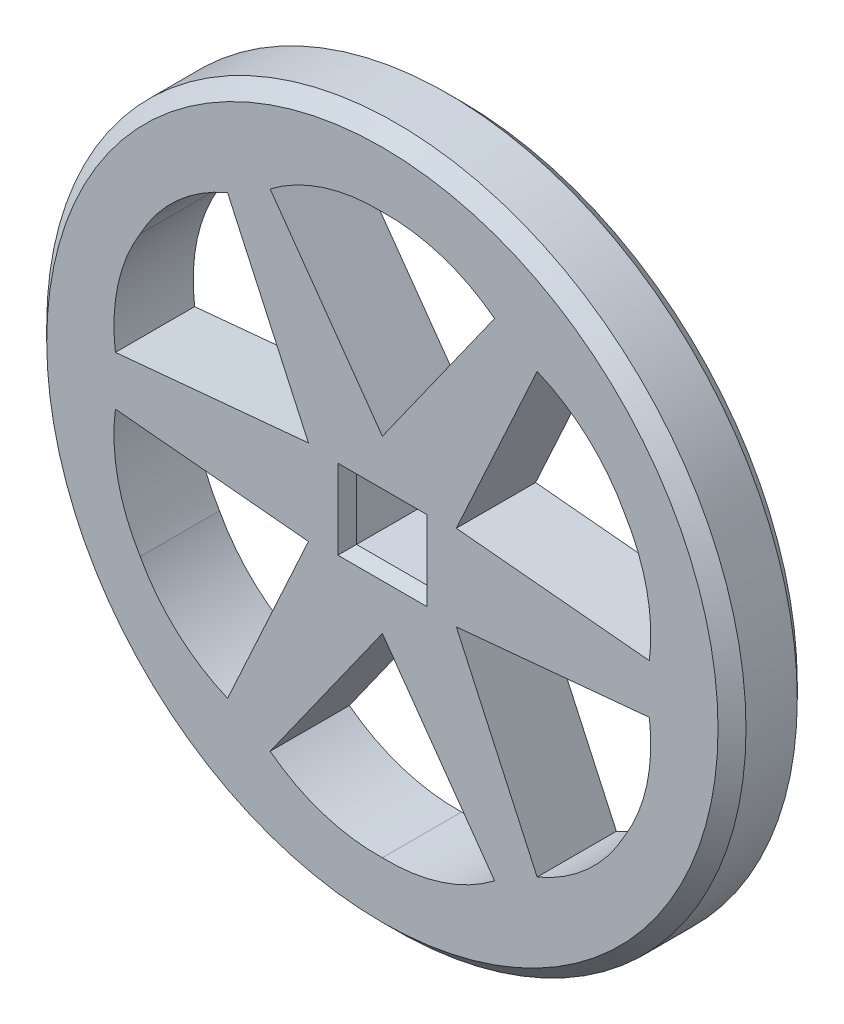
SolidWorks part; units mm, degrees
ref_plane "Front Plane" through (0, 0, 0) normal (0, 0, 1) x (1, 0, 0)
ref_plane "Top Plane" through (0, 0, 0) normal (0, 1, 0) x (1, 0, 0)
ref_plane "Right Plane" through (0, 0, 0) normal (1, 0, 0) x (0, 0, -1)
sketch "Sketch1" plane through (0, 0, 0) normal (0, 0, 1) x (1, 0, 0)
  line L1 (4.275, -3.775) -> (-4.275, -3.775)
  line L2 (4.275, -3.775) -> (4.275, 3.775)
  line L3 (4.275, 3.775) -> (-4.275, 3.775)
  line L4 (-4.275, -3.775) -> (-4.275, 3.775)
  circle A0 centre (0, 0) radius 37.5
  point P3 (0, 3.775)
  point P9 (4.275, 0)
  dimension "D1" = 75
  dimension "D2" = 8.55
  dimension "D3" = 7.55
extrude "Boss-Extrude1" add sketch "Sketch1" along normal mid plane 8.5
sketch "Sketch2" plane through (0, 0, 0) normal (0, 0, 1) x (1, 0, 0)
  line L0 (0, 0) -> (0, 32.5712) construction
  line L1 (0, 9.1586) -> (-12.0371, 26.1152)
  line L2 (0, 9.1586) -> (12.0371, 26.1152)
  arc A0 (-12.0371, 26.1152) -> (0, 29.9881) centre (-0.5568, 11.0765) cw
  arc A1 (12.0371, 26.1152) -> (0, 29.9881) centre (0.5568, 11.0765) ccw
extrude "Cut-Extrude1" cut sketch "Sketch2" along normal through all both and the other way through all
pattern_circular "CirPattern1" count 6 over 360 about axis through (0, 0, 4.25) along (0, 0, -1) of "Cut-Extrude1" reverse direction yes
sketch "Sketch3" plane through (0, 0, 0) normal (0, 0, 1) x (1, 0, 0)
  circle A0 centre (0, 0) radius 37.5
  circle A1 centre (0, 0) radius 37.2
  circle A2 centre (0, 0) radius 37.5 construction
  dimension "D1" = 0.3
chamfer "Chamfer1" distance 0.5 distance2 1.5 4 edges at (4.275, 0, 4.25) (0, 3.775, 4.25) (-4.275, 0, 4.25) (0, -3.775, 4.25) first distance on face at (37.5, 0, 4.25)
chamfer "Chamfer2" distance 1.5 angle 45 2 edges at (37.5, 0, 4.25) (37.5, 0, -4.25)
sketch "Sketch4" plane through (0, 0, 4.25) normal (0, 0, 1) x (1, 0, 0)
  line L0 (0, 4.275) -> (0, -4.275) construction
  line L1 (-4.775, 4.275) -> (4.775, 4.275) construction
  line L2 (4.775, -4.275) -> (-4.775, -4.275) construction
  line L3 (-4.775, 0) -> (4.775, 0) construction
  line L4 (-4.775, -4.275) -> (-4.775, 4.275) construction
  line L5 (4.775, 4.275) -> (4.775, -4.275) construction
